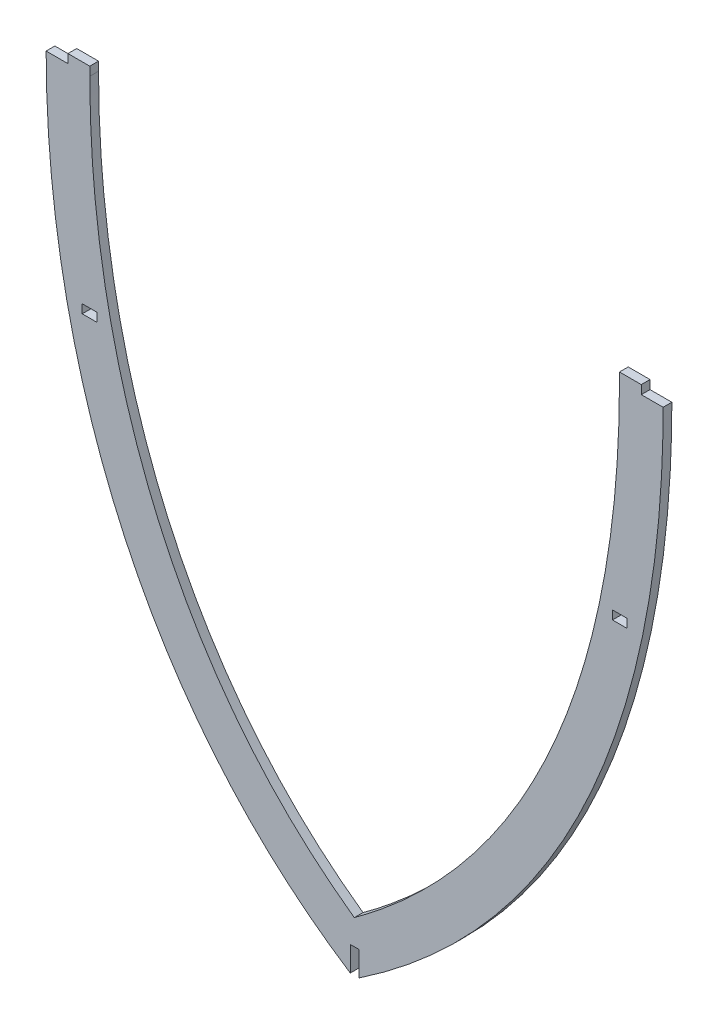
SolidWorks part; units mm, degrees
material "birch 3mm plywood"
ref_plane "Front" through (0, 0, 0) normal (0, 0, 1) x (1, 0, 0)
ref_plane "Top" through (0, 0, 0) normal (0, 1, 0) x (1, 0, 0)
ref_plane "Right" through (0, 0, 0) normal (1, 0, 0) x (0, 0, -1)
sketch "Sketch1" plane through (0, 0, 0) normal (0, 0, 1) x (1, 0, 0)
  line L0 (88.6, -155) -> (88.6, -152) construction
  line L1 (93.6, -155) -> (93.6, -152) construction
  line L2 (98.6, -152) -> (93.6, -152) construction
  line L8 (-88.6, -152) -> (-93.6, -152)
  line L9 (-93.6, -152) -> (-93.6, -155)
  line L10 (-93.6, -155) -> (-88.6, -155)
  line L11 (-88.6, -155) -> (-88.6, -152)
  line L12 (93.6, -152) -> (88.6, -152)
  line L13 (88.6, -152) -> (88.6, -155)
  line L14 (88.6, -155) -> (93.6, -155)
  line L15 (93.6, -155) -> (93.6, -152)
  line L16 (-106, -83) -> (-98.5, -83)
  line L17 (-106, -83) -> (-68.5834, -83) construction
  line L18 (-98.5, -83) -> (-98.5, -80)
  line L19 (-68.5834, -80) -> (-106, -80) construction
  line L20 (-98.5, -80) -> (-91, -80)
  line L21 (-91, -80) -> (-91, -83)
  line L22 (106, -83) -> (98.5, -83)
  line L23 (68.5834, -83) -> (106, -83) construction
  line L24 (98.5, -83) -> (98.5, -80)
  line L25 (106, -80) -> (68.5834, -80) construction
  line L26 (98.5, -80) -> (91, -80)
  line L27 (91, -80) -> (91, -83)
  spline S0 degree 3 poles (-689.1218, -689.4456) (-526.188, 2005.1664) (1179.2665, -1293.1937) (-971.9139, -70.897) knots -4.713827 -4.713827 -4.713827 -4.713827 2.888359 2.888359 2.888359 2.888359 only from (106, -83) to (0, -306.0893) construction
  spline S1 degree 3 poles (527.7085, -856.5676) (101.6854, 1680.995) (-837.4964, -1387.3871) (926.4192, 70.3685) knots -3.56249 -3.56249 -3.56249 -3.56249 2.834074 2.834074 2.834074 2.834074 only from (-106, -83) to (0, -306.0893) construction
  spline S2 degree 3 poles (106, -83) (106, -174.4433) (74.7629, -256.783) (0, -306.0893) knots 0 0 0 0 1 1 1 1
  spline S3 degree 3 poles (-106, -83) (-106, -171.1717) (-74.7629, -258.4392) (0, -306.0893) knots 0 0 0 0 1 1 1 1
  spline S4 degree 1 poles (-91, -83) (-0.1167, -287.9264) knots 0 0 1 1 construction
  spline S5 degree 1 poles (91, -83) (-0.1167, -287.9264) knots 0 0 1 1 construction
  spline S6 degree 3 poles (-91, -83) (-91, -88.0686) (-90.7842, -98.2205) (-89.4717, -118.3778) (-86.1468, -143.2308) (-79.3681, -172.0711) (-69.7174, -199.532) (-57.1183, -225.2317) (-44.0961, -244.8889) (-32.112, -259.4019) (-22.3248, -269.6427) (-13.4811, -277.6134) (-5.9927, -283.6258) (-2.0894, -286.5211) (-0.1167, -287.9264) knots 0 0 0 0 0.059983 0.119967 0.239934 0.359901 0.479868 0.599835 0.719802 0.779785 0.839769 0.899752 0.929744 0.959735 0.959735 0.959735 0.959735
  spline S7 degree 3 poles (-0.1167, -287.9264) (1.8708, -286.4802) (5.8114, -283.5064) (13.356, -277.3846) (22.2576, -269.3453) (32.0901, -259.1217) (44.1097, -244.7411) (57.1396, -225.4116) (69.7252, -200.2046) (79.363, -173.1605) (85.0093, -149.2619) (88.136, -129.4393) (89.7964, -114.2526) (90.6189, -101.351) (90.9458, -90.91) (91, -85.632) (91, -83) knots 0 0 0 0 0.030008 0.060016 0.120032 0.180048 0.240064 0.360096 0.480129 0.600161 0.720193 0.780209 0.840225 0.900241 0.930249 0.960257 0.960257 0.960257 0.960257
  dimension "D2" = 7.5
  dimension "D3" = 7.5
  dimension "D1" = 15
extrude "Boss-Extrude1" add sketch "Sketch1" along normal mid plane 3
sketch "Sketch2" plane through (0, 0, 1.5) normal (0, 0, 1) x (1, 0, 0)
  line L0 (-1.5, -296.5952) -> (1.5, -296.5952)
  line L1 (1.5, -296.5952) -> (1.5, -306.0893)
  line L2 (1.5, -306.0893) -> (-1.5, -306.0893)
  line L3 (1.5, -306.0893) -> (-1.5, -306.0893) construction
  line L4 (-1.5, -83) -> (-1.5, -306.0893) construction
  line L5 (-1.5, -306.0893) -> (-1.5, -296.5952)
extrude "Cut-Extrude1" cut sketch "Sketch2" against normal blind 3
